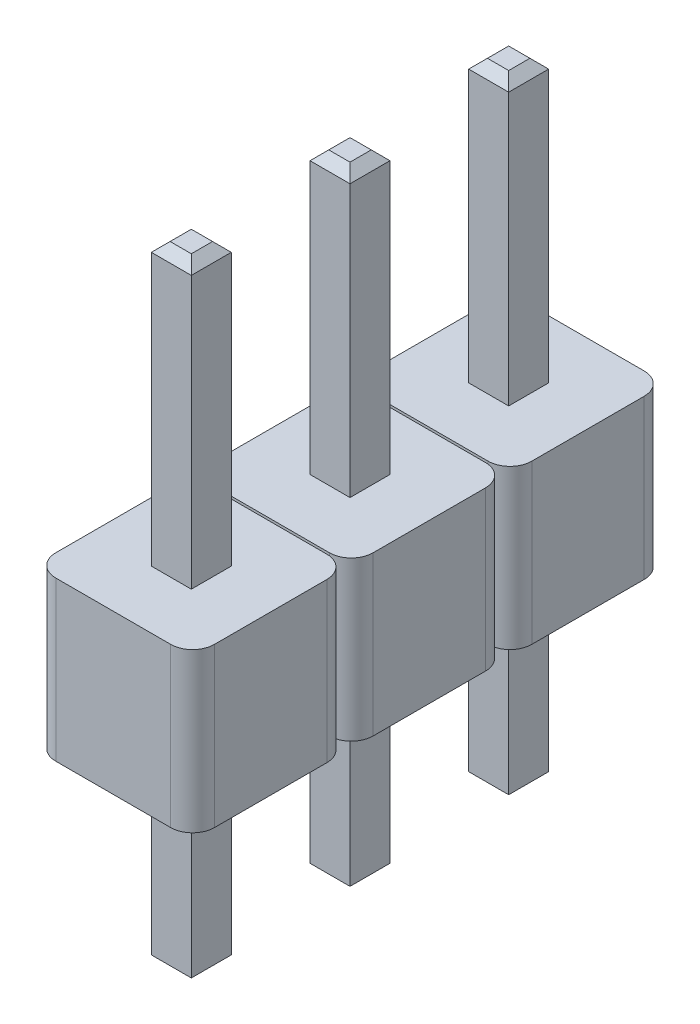
SolidWorks part; units mm, degrees
ref_plane "Front Plane" through (0, 0, 0) normal (0, 0, 1) x (1, 0, 0)
ref_plane "Top Plane" through (0, 0, 0) normal (0, 1, 0) x (1, 0, 0)
ref_plane "Right Plane" through (0, 0, 0) normal (1, 0, 0) x (0, 0, -1)
sketch "Sketch1" plane through (0, 0, 0) normal (0, 1, 0) x (1, 0, 0)
  line L1 (0, 0) -> (0.64, 0)
  line L2 (0, 0) -> (0, 0.64)
  line L3 (0, 0.64) -> (0.64, 0.64)
  line L4 (0.64, 0) -> (0.64, 0.64)
  dimension "D1" = 0.64
  dimension "D2" = 0.64
extrude "Boss-Extrude1" add sketch "Sketch1" along normal blind 10.04
chamfer "Chamfer1" distance 0.15 angle 45 8 edges at (0.32, 0, 0) (0.64, 0, -0.32) (0.32, 0, -0.64) (0, 0, -0.32) (0.32, 10.04, -0.64) (0.64, 10.04, -0.32) (0.32, 10.04, 0) (0, 10.04, -0.32)
ref_plane "Plane1" through (0, 5.54, 0) normal (0, 1, 0) x (1, 0, 0)
sketch "Sketch3" plane through (0, 5.54, 0) normal (0, 1, 0) x (1, 0, 0)
  line L0 (0.32, 0.64) -> (0.32, 0) construction
  line L1 (0, 0.64) -> (0.64, 0.64) construction
  line L2 (0.64, 0) -> (0, 0) construction
  line L4 (-0.6, -0.93) -> (1.24, -0.93)
  line L5 (-0.95, -0.58) -> (-0.95, 1.22)
  line L6 (-0.6, 1.57) -> (1.24, 1.57)
  line L7 (1.59, -0.58) -> (1.59, 1.22)
  line L8 (-0.95, -0.93) -> (1.59, 1.57) construction
  line L9 (-0.95, 1.57) -> (1.59, -0.93) construction
  arc A0 (-0.6, -0.93) -> (-0.95, -0.58) centre (-0.6, -0.58) cw
  arc A1 (1.24, 1.57) -> (1.59, 1.22) centre (1.24, 1.22) cw
  arc A2 (-0.95, 1.22) -> (-0.6, 1.57) centre (-0.6, 1.22) cw
  arc A3 (1.24, -0.93) -> (1.59, -0.58) centre (1.24, -0.58) ccw
  point P6 (0.32, 0.32)
  point P7 (0.32, 0.32)
  dimension "D3" = 0.35
  dimension "D1" = 2.5
  dimension "D2" = 2.54
extrude "Boss-Extrude2" add sketch "Sketch3" against normal blind 2.54
ref_axis "Axis1" through (0.32, 3, 0.93) along (0, 0, -1)
pattern_linear "LPattern2" count 3 spacing 2.54 along (0, 0, -1) of bodies 102
